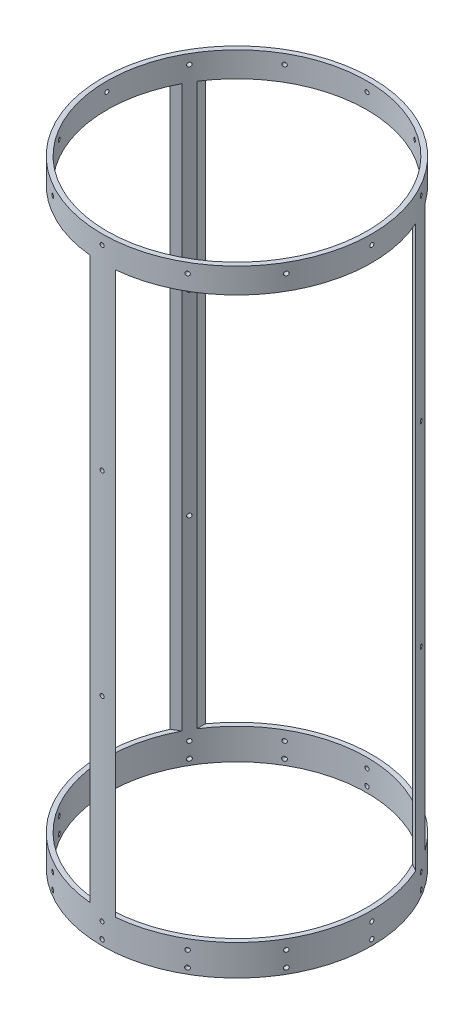
SolidWorks part; units mm, degrees
material "6061-T6 (SS)"
ref_plane "Front Plane" through (0, 0, 0) normal (0, 0, 1) x (1, 0, 0)
ref_plane "Top Plane" through (0, 0, 0) normal (0, 1, 0) x (1, 0, 0)
ref_plane "Right Plane" through (0, 0, 0) normal (1, 0, 0) x (0, 0, -1)
sketch "Sketch1" plane through (0, 0, 0) normal (0, 1, 0) x (1, 0, 0)
  circle A0 centre (0, 0) radius 88.9
  circle A1 centre (0, 0) radius 85.725
  dimension "D1" = 177.8
  dimension "D2" = 171.45
extrude "Boss-Extrude1" add sketch "Sketch1" along normal mid plane 406.4
sketch "Sketch2" plane through (0, 0, 0) normal (0, 0, 1) x (1, 0, 0)
  line L0 (85.725, 203.2) -> (-85.725, 203.2) construction
  line L1 (-72.39, -182.88) -> (72.39, -182.88)
  line L2 (-72.39, -182.88) -> (-72.39, 186.69)
  line L3 (-72.39, 186.69) -> (72.39, 186.69)
  line L4 (72.39, -182.88) -> (72.39, 186.69)
  line L5 (-72.39, -182.88) -> (72.39, 186.69) construction
  line L6 (-72.39, 186.69) -> (72.39, -182.88) construction
  line L7 (88.9, -203.2) -> (88.9, 203.2) construction
  line L8 (-88.9, 203.2) -> (-88.9, -203.2) construction
  line L9 (-88.9, -203.2) -> (88.9, -203.2) construction
  point P0 (0, 0)
  dimension "D1" = 16.51
  dimension "D2" = 16.51
  dimension "D3" = 16.51
  dimension "D4" = 20.32
extrude "Cut-Extrude1" cut sketch "Sketch2" against normal up to surface (51.6033 mm away) up to face at (0, 203.2, 88.9)
pattern_circular "CirPattern1" count 3 over 360 about axis through (0, 203.2, 0) along (0, -1, 0) of "Cut-Extrude1"
ref_plane "Plane1" through (88.9, 0, 0) normal (1, 0, 0) x (0, 0, -1)
sketch "Sketch3" plane through (88.9, 0, 0) normal (1, 0, 0) x (0, 0, -1)
  line L0 (36.8899, -182.88) -> (-88.4932, -182.88) construction
  line L1 (-88.9, -203.2) -> (88.9, -203.2) construction
  circle A0 centre (0, -199.39) radius 1.4351
  circle A1 centre (0, -189.23) radius 1.3525
  dimension "D1" = 3.81
  dimension "D2" = 2.8702
  dimension "D3" = 2.7051
  dimension "D4" = 6.35
extrude "Cut-Extrude2" cut sketch "Sketch3" against normal blind 15.24
pattern_circular "CirPattern2" count 12 over 360 about axis through (0, 203.2, 0) along (0, -1, 0) of "Cut-Extrude2" reverse direction yes
sketch "Sketch4" plane through (88.9, 0, 0) normal (1, 0, 0) x (0, 0, -1)
  line L0 (0, 97.79) -> (0, -97.79) construction
  line L1 (88.9, 203.2) -> (-88.9, 203.2) construction
  circle A0 centre (0, 196.85) radius 1.3525
  dimension "D1" = 2.7051
  dimension "D2" = 6.35
extrude "Cut-Extrude3" cut sketch "Sketch4" against normal blind 15.24
pattern_circular "CirPattern3" count 12 over 360 about axis through (0, 203.2, 0) along (0, -1, 0) of "Cut-Extrude3"
ref_plane "Plane2" through (0, 0, 88.9) normal (0, 0, 1) x (1, 0, 0)
sketch "Sketch5" plane through (0, 0, 88.9) normal (0, 0, 1) x (1, 0, 0)
  circle A0 centre (0, 68.1736) radius 1.3526
  circle A1 centre (0, -60.5536) radius 1.3526
  circle A2 centre (0, 196.85) radius 1.3525 construction
  circle A3 centre (0, -189.23) radius 1.3526 construction
  dimension "D1" = 128.6764
  dimension "D2" = 128.6764
  dimension "D3" = 2.7051
  dimension "D4" = 2.7051
extrude "Cut-Extrude4" cut sketch "Sketch5" against normal blind 35.56
pattern_circular "CirPattern4" count 3 over 360 about axis through (0, 203.2, 0) along (0, -1, 0) of "Cut-Extrude4"
